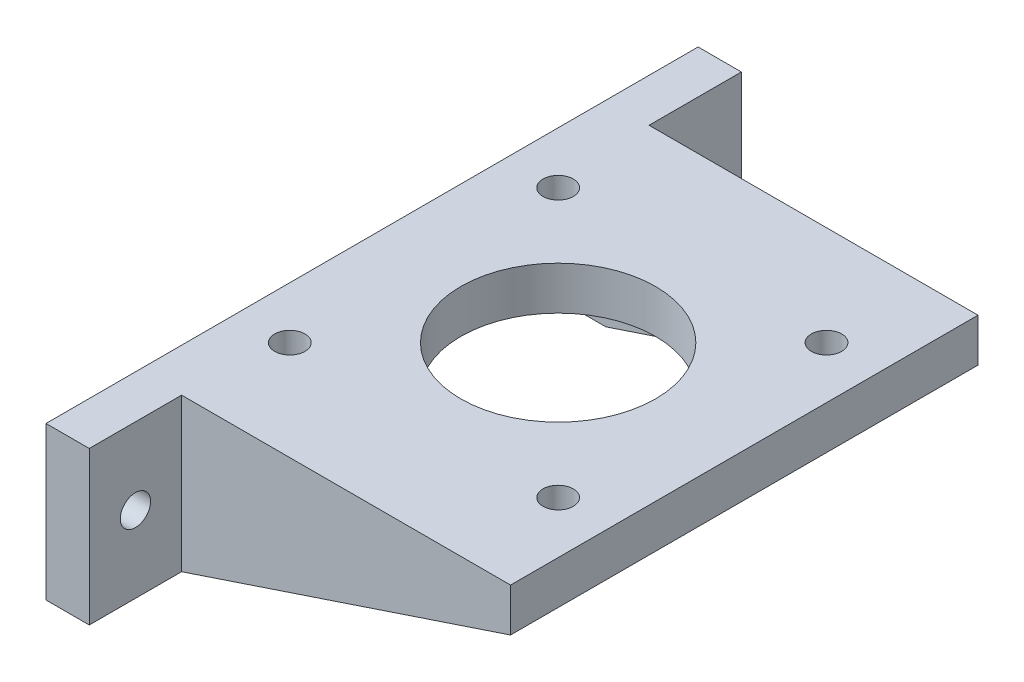
SolidWorks part; units mm, degrees
material "ABS"
ref_plane "Front Plane" through (0, 0, 0) normal (0, 0, 1) x (1, 0, 0)
ref_plane "Top Plane" through (0, 0, 0) normal (0, 1, 0) x (1, 0, 0)
ref_plane "Right Plane" through (0, 0, 0) normal (1, 0, 0) x (0, 0, -1)
sketch "Sketch1" plane through (0, 0, 0) normal (0, 0, 1) x (1, 0, 0)
  line L0 (5, 5) -> (43, 5)
  line L1 (0, 0) -> (5, 0)
  line L2 (0, 0) -> (0, 5)
  line L3 (0, 5) -> (5, 5)
  line L4 (5, 0) -> (5, 5)
  line L5 (43, 5) -> (43, 0)
  line L6 (43, 0) -> (5, 0)
  line L7 (5, 0) -> (5, -12.666)
  line L8 (5, -12.666) -> (0, -12.666)
  line L9 (0, -12.666) -> (0, 0)
  line L10 (5, -12.666) -> (43, 0)
  dimension "D1" = 5
  dimension "D2" = 5
  dimension "D3" = 43
  dimension "D4" = 12.666
extrude "Boss-Extrude1" add sketch "Sketch1" against normal blind 44 contours L1 L4 L3 L2 | L6 L5 L0 L4 region at (2.5, 2.5, 0) region at (24, 2.5, 0)
sketch "Sketch2" plane through (0, 5, 0) normal (0, 1, 0) x (1, 0, 0)
  line L3 (0, 44) -> (0, 0) construction
  line L4 (0, 0) -> (43, 0) construction
  circle A0 centre (21.5, 22) radius 11.25
  circle A1 centre (37, 37.5) radius 1.75
  circle A2 centre (6, 37.5) radius 1.75
  circle A3 centre (6, 6.5) radius 1.75
  circle A4 centre (37, 6.5) radius 1.75
  dimension "D3" = 22.5
  dimension "D4" = 3.5
  dimension "D1" = 21.5
  dimension "D2" = 22
  dimension "D5" = 15.5
  dimension "D6" = 15.5
  dimension "D7" = 2
  dimension "D8" = 2
extrude "Cut-Extrude1" cut sketch "Sketch2" against normal through all
extrude "Boss-Extrude2" add sketch "Sketch1<3>" along normal blind 5 contours L7 L10 L6 | L6 L5 L0 L4 | L1 L4 L3 L2 | L9 L8 L7 L1 region at (2.5, 2.5, 0) region at (24, 2.5, 0) region at (2.5, -6.333, 0) region at (17.6667, -4.222, 0)
sketch "Sketch1<3>" plane through (0, 0, 0) normal (0, 0, 1) x (1, 0, 0) same geometry as "Sketch1"
extrude "Boss-Extrude3" add sketch "Sketch1<4>" against normal blind 5 from vertex contours L1 L4 L3 L2 | L9 L8 L7 L1 | L7 L10 L6 | L6 L5 L0 L4 region at (2.5, 2.5, 0) region at (24, 2.5, 0) region at (2.5, -6.333, 0) region at (17.6667, -4.222, 0) starting at point (0, 5, -44)
sketch "Sketch1<4>" plane through (0, 0, 0) normal (0, 0, 1) x (1, 0, 0) same geometry as "Sketch1"
sketch "Sketch3" plane through (0, 0, 0) normal (-1, 0, 0) x (0, 0, 1)
  line L0 (5, -12.666) -> (0, -12.666) construction
  line L1 (5, 5) -> (15.666, 5)
  line L2 (5, 5) -> (5, -12.666)
  line L3 (5, -12.666) -> (15.666, -12.666)
  line L4 (15.666, 5) -> (15.666, -12.666)
  line L5 (10.333, 5) -> (10.333, -12.666) construction
  line L6 (15.666, -3.833) -> (5, -3.833) construction
  line L7 (-22, 5) -> (-22, 0) construction
  line L8 (-49, 5) -> (5, 5) construction
  line L9 (-44, 0) -> (0, 0) construction
  line L10 (-49, -12.666) -> (-59.666, -12.666)
  line L11 (-59.666, 5) -> (-59.666, -12.666)
  line L12 (-54.333, 5) -> (-54.333, -12.666) construction
  line L13 (-59.666, -3.833) -> (-49, -3.833) construction
  line L14 (-49, 5) -> (-49, -12.666)
  line L15 (-49, 5) -> (-59.666, 5)
  circle A0 centre (10.333, -3.833) radius 1.75
  circle A1 centre (-54.333, -3.833) radius 1.75
  dimension "D2" = 3.5
  dimension "D1" = 10.666
extrude "Boss-Extrude4" add sketch "Sketch3" against normal blind 5
equation "\"rod_diameter\"= 8"
equation "\"rod_hole_thickness\"= 4"
equation "\"rod_radius\"= \"rod_diameter\" / 2"
equation "\"platter_diameter\"= 320"
equation "\"platter_radius\"= \"platter_diameter\" / 2"
equation "\"extruder_mount_hole_spacing\"= 75"
equation "\"arm_rod_spacing\"= 40"
equation "\"D2@Sketch2\" = \"D1@Boss-Extrude1\" / 2"
equation "\"motor_level_rod_spacing\"= 15"
equation "\"top_frame_spacing\"= 100"
equation "\"linear_bearing_diameter\"= 15"
equation "\"z_rod_spacing\"= 75"
equation "\"platter_rod_spacing\"= 50"
equation "\"rod_nut_thickness\"= 6.5"
equation "\"rod_nut_inscribed_diameter\"= 13"
equation "\"z_height\"= 400"
equation "\"gear_pitch\"=2"
equation "\"r_gear_teeth\"= 450"
equation "\"theta_gear_teeth\"= 385"
equation "\"sheet_thickness\"=5.333"
equation "\"sheet_tab_hole_thickness\"= \"sheet_thickness\""
equation "\"sheet_tab_width\"= \"sheet_thickness\"*2"
equation "\"sheet_bolt_diameter\"= 3"
equation "\"sheet_bolt_length\"= 16"
equation "\"sheet_nut_diameter\"= 5.5"
equation "\"sheet_nut_thickness\"= 2.5"
equation "\"sheet_nut_depth\"= 10"
equation "\"bearing_outside_diameter\"= 22"
equation "\"bearing_thickness\"= 7"
equation "\"corner_part_thickness\"= \"sheet_thickness\" + \"bearing_thickness\""
equation "\"D4@Sketch1\"=\"sheet_thickness\"*2+7-\"D1@Sketch1\""
equation "\"D1@Sketch2\"= \"D3@Sketch1\" / 2"
equation "\"D1@Sketch3\"=\"sheet_thickness\"*2"
equation "\"D2@Sketch3\"=\"sheet_bolt_diameter\"+\"printed_hole_tolerance\""
equation "\"z_drive_rod_offset\"= 12"
equation "\"sheet_double_tab_width\"= 35"
equation "\"setscrew_nut_diameter\"= 6"
equation "\"setscrew_nut_thickness\"= 3"
equation "\"setscrew_bolt_diameter\"= 3"
equation "\"motor_shaft_diameter\"= 5.7"
equation "\"printed_hole_tolerance\"= 0.5"
equation "\"D4@Sketch2\"=3 +\"printed_hole_tolerance\""
equation "\"D3@Sketch2\"=22 +\"printed_hole_tolerance\""
